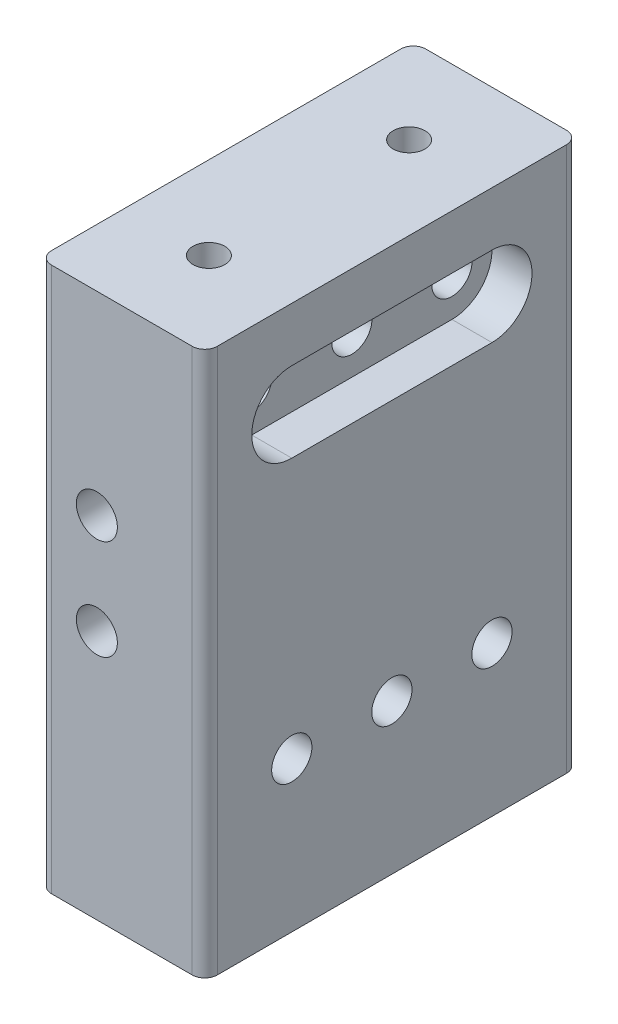
SolidWorks part; units mm, degrees
material "PET"
ref_plane "Front Plane" through (0, 0, 0) normal (0, 0, 1) x (1, 0, 0)
ref_plane "Top Plane" through (0, 0, 0) normal (0, 1, 0) x (1, 0, 0)
ref_plane "Right Plane" through (0, 0, 0) normal (1, 0, 0) x (0, 0, -1)
sketch "Sketch1" plane through (0, 0, 0) normal (0, 1, 0) x (1, 0, 0)
  line L1 (-10.5156, -23.7427) -> (10.5156, -23.7427)
  line L2 (-10.5156, -23.7427) -> (-10.5156, 23.7426)
  line L3 (-10.5156, 23.7426) -> (10.5156, 23.7426)
  line L4 (10.5156, -23.7427) -> (10.5156, 23.7426)
  line L5 (-10.5156, -23.7427) -> (10.5156, 23.7426) construction
  line L6 (-10.5156, 23.7426) -> (10.5156, -23.7427) construction
  point P0 (0, 0)
  dimension "D1" = 21.0312
  dimension "D2" = 47.4853
extrude "Boss-Extrude1" add sketch "Sketch1" along normal mid plane 63.5
sketch "Sketch2" plane through (0, 0, 23.7427) normal (0, 0, 1) x (1, 0, 0)
  line L5 (-10.5156, 31.75) -> (10.5156, 31.75) construction
  circle A1 centre (-3.175, 0) radius 2.6035
  circle A2 centre (-3.175, 12.7) radius 2.6035
  circle A3 centre (-3.175, -12.7) radius 2.6035
  dimension "D3" = 19.05
  dimension "D1" = 13.6906
  dimension "D2" = 5.207
  dimension "D4" = 12.7
  dimension "D5" = 12.7
extrude "Cut-Extrude1" cut sketch "Sketch2" against normal through all contours A2 | A1 region at (-3.175, 0, 23.7427) region at (-3.175, 12.7, 23.7427)
sketch "Sketch4" plane through (10.5156, 0, 0) normal (1, 0, 0) x (0, 0, -1)
  line L0 (-23.7427, 31.75) -> (23.7426, 31.75) construction
  circle A0 centre (-12.7, 25.4) radius 2.5527
  circle A1 centre (12.7, 25.4) radius 2.5527
  circle A2 centre (0, 25.4) radius 2.5527
  dimension "D5" = 5.1054
  dimension "D1" = 6.35
  dimension "D3" = 12.7
  dimension "D4" = 12.7
extrude "Cut-Extrude3" cut sketch "Sketch4" against normal through all
fillet "Fillet1" radius 1.5875 4 edges at (10.5156, 0, 23.7427) (-10.5156, 0, 23.7427) (-10.5156, 0, -23.7426) (10.5156, 0, -23.7426)
sketch "Sketch7" plane through (10.5156, 0, 0) normal (1, 0, 0) x (0, 0, -1)
  line L0 (-12.7, 25.4) -> (12.7, 25.4) construction
  line L1 (-12.7, 30.48) -> (12.7, 30.48)
  line L2 (-12.7, 20.32) -> (12.7, 20.32)
  arc A0 (-12.7, 30.48) -> (-12.7, 20.32) centre (-12.7, 25.4) ccw
  arc A1 (12.7, 20.32) -> (12.7, 30.48) centre (12.7, 25.4) ccw
  point P4 (0, 25.4)
  dimension "D1" = 5.08
extrude "Cut-Extrude5" cut sketch "Sketch7" against normal blind 5.08
sketch "Sketch8" plane through (0, 31.75, 0) normal (0, 1, 0) x (1, 0, 0)
  line L4 (-8.9281, -23.7427) -> (8.9281, -23.7427)
  line L5 (10.5156, -22.1552) -> (10.5156, 22.1551)
  line L6 (8.9281, 23.7426) -> (-8.9281, 23.7426)
  line L7 (-10.5156, 22.1551) -> (-10.5156, -22.1552)
  line L8 (-8.9281, -23.7427) -> (8.9281, -23.7427)
  line L9 (10.5156, -22.1552) -> (10.5156, 22.1551)
  line L10 (8.9281, 23.7426) -> (-8.9281, 23.7426)
  line L11 (-10.5156, 22.1551) -> (-10.5156, -22.1552)
  arc A4 (8.9281, -23.7427) -> (10.5156, -22.1552) centre (8.9281, -22.1552) ccw
  arc A5 (10.5156, 22.1551) -> (8.9281, 23.7426) centre (8.9281, 22.1551) ccw
  arc A6 (-8.9281, 23.7426) -> (-10.5156, 22.1551) centre (-8.9281, 22.1551) ccw
  arc A7 (-8.9281, 23.7426) -> (-10.5156, 22.1551) centre (-8.9281, 22.1551) ccw
  arc A8 (8.9281, -23.7427) -> (10.5156, -22.1552) centre (8.9281, -22.1552) ccw
  arc A9 (10.5156, 22.1551) -> (8.9281, 23.7426) centre (8.9281, 22.1551) ccw
  arc A10 (-10.5156, -22.1552) -> (-8.9281, -23.7427) centre (-8.9281, -22.1552) ccw
  arc A11 (-10.5156, -22.1552) -> (-8.9281, -23.7427) centre (-8.9281, -22.1552) ccw
  dimension "D1" = 0
extrude "Boss-Extrude2" add sketch "Sketch8" along normal blind 5.588
sketch "Sketch9" plane through (0, 37.338, 0) normal (0, 1, 0) x (1, 0, 0)
  line L0 (-10.5156, 0) -> (10.5156, 0) construction
  line L1 (-10.5156, 22.1551) -> (-10.5156, -22.1552) construction
  line L2 (10.5156, -22.1552) -> (10.5156, 22.1551) construction
  circle A0 centre (0, 12.7) radius 2.0193
  circle A2 centre (0, -12.7) radius 2.0193
  dimension "D2" = 4.0386
  dimension "D1" = 12.7
  dimension "D3" = 10.5156
extrude "Cut-Extrude6" cut sketch "Sketch9" against normal blind 5.08
sketch "Sketch10" plane through (10.5156, 0, 0) normal (1, 0, 0) x (0, 0, -1)
  line L1 (-22.1552, -31.75) -> (22.1551, -31.75) construction
  circle A0 centre (0, -12.7) radius 2.5527
  circle A1 centre (12.7, -12.7) radius 2.5527
  circle A2 centre (-12.7, -12.7) radius 2.5527
  dimension "D1" = 5.1054
  dimension "D2" = 12.7
  dimension "D3" = 12.7
  dimension "D4" = 19.05
extrude "Cut-Extrude7" cut sketch "Sketch10" against normal through all
